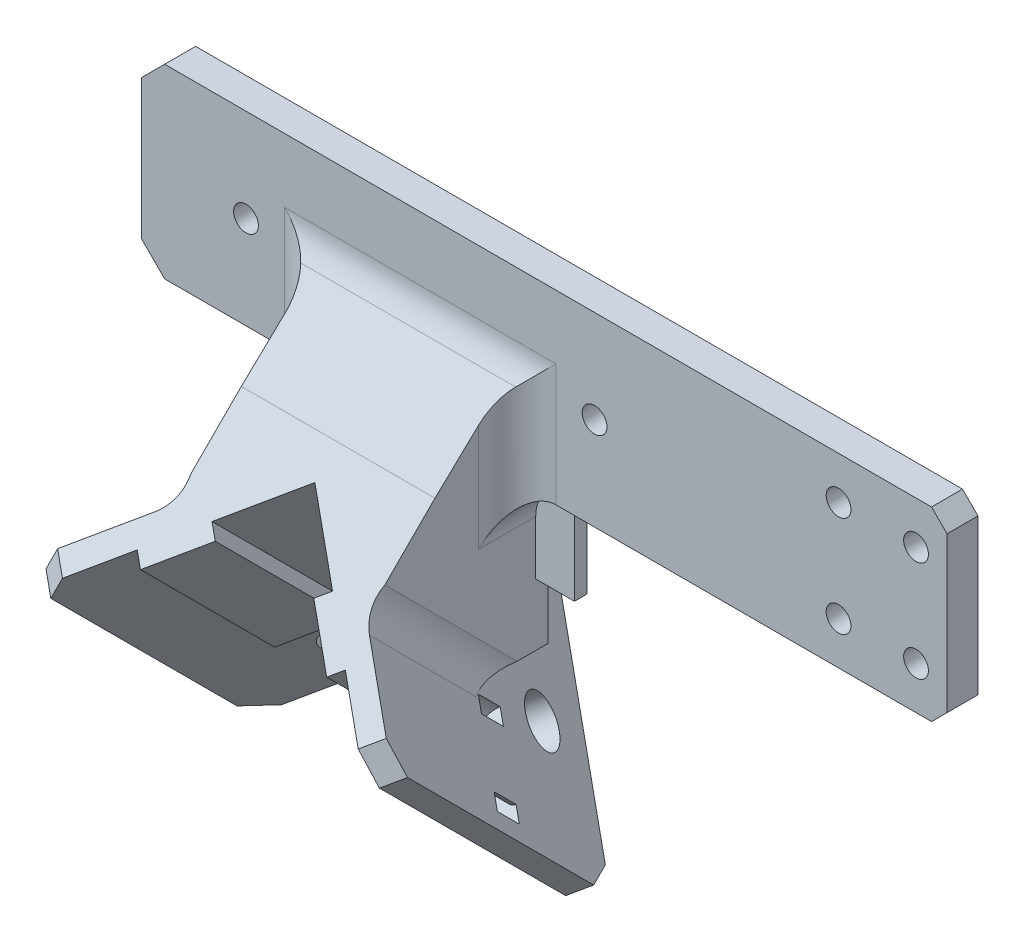
SolidWorks part; units mm, degrees
ref_plane "Alzado" through (0, 0, 0) normal (0, 0, 1) x (1, 0, 0)
ref_plane "Planta" through (0, 0, 0) normal (0, 1, 0) x (1, 0, 0)
ref_plane "Vista lateral" through (0, 0, 0) normal (1, 0, 0) x (0, 0, -1)
sketch "Croquis1" plane through (0, 0, 0) normal (0, 0, 1) x (1, 0, 0)
  line L0 (0, 0) -> (0, 18835.1574) construction
  line L1 (0, 0) -> (-18835.1574, 0) construction
  line L2 (12.5, -12) -> (36, -12)
  line L3 (-36, -12) -> (36, -12) construction
  line L4 (-36, -12) -> (-36, 12)
  line L5 (-36, 12) -> (36, 12)
  line L6 (36, -12) -> (36, 12)
  line L7 (-36, -12) -> (36, 12) construction
  line L8 (-36, 12) -> (36, -12) construction
  line L9 (-17.5, 6) -> (17.5, 6) construction
  line L10 (-17.5, 6) -> (-17.5, -6) construction
  line L11 (-17.5, -6) -> (17.5, -6) construction
  line L12 (17.5, 6) -> (17.5, -6) construction
  line L13 (-17.5, 6) -> (17.5, -6) construction
  line L14 (-17.5, -6) -> (17.5, 6) construction
  line L15 (-12.5, -32) -> (12.5, -32)
  line L16 (-12.5, -32) -> (-12.5, -12)
  line L17 (-12.5, -12) -> (12.5, -12) construction
  line L18 (12.5, -32) -> (12.5, -12)
  line L19 (-12.5, -32) -> (12.5, -12) construction
  line L20 (-12.5, -12) -> (12.5, -32) construction
  line L21 (-36, -12) -> (-12.5, -12)
  circle A0 centre (-22.5, 0) radius 1.6
  circle A1 centre (22.5, 0) radius 1.6
  point P7 (0, 0)
  point P12 (0, -22)
  point P16 (0, 0)
  dimension "D1" = 3.2
  dimension "D2" = 45
  dimension "D3" = 24
  dimension "D4" = 13.5
  dimension "D5" = 35
  dimension "D6" = 12
  dimension "D7" = 20
  dimension "D8" = 25
extrude "Saliente-Extruir1" add sketch "Croquis1" along normal blind 4
sketch "Croquis3" plane through (0, 0, 0) normal (0, 0, -1) x (-1, 0, 0)
  line L0 (0, 0) -> (-50000, 0) construction
  line L1 (-66, 12) -> (-36, 12)
  line L2 (-66, -12) -> (-36, -12)
  line L3 (-36, -12) -> (-36, 12)
  line L4 (-36, -12) -> (-36, 12) construction
  line L5 (-66, 12) -> (-68, 10)
  line L6 (-68, 10) -> (-68, -10)
  line L7 (-66, -12) -> (-68, -10)
  arc A0 (-66, 12) -> (-66, -12) centre (-66, 0) ccw construction
  circle A1 centre (-54, 6.5) radius 1.6
  circle A2 centre (-64, 6.5) radius 1.6
  circle A3 centre (-54, -6.5) radius 1.6
  circle A4 centre (-64, -6.5) radius 1.6
  point P22 (-68, 0)
  dimension "D1" = 30
  dimension "D2" = 3.2
  dimension "D5" = 28
  dimension "D3" = 13
  dimension "D4" = 18
  dimension "D6" = 32
  dimension "D7" = 2
extrude "Saliente-Extruir3" add sketch "Croquis3" against normal blind 4
ref_plane "Plano1" through (0, -4, -4) normal (0, -0.7071, -0.7071) x (1, 0, 0)
sketch "Croquis5" plane through (0, -4.201, -3.799) normal (0, 0.7071, 0.7071) x (1, 0, 0)
  line L0 (0, 0) -> (0, 50000) construction
  line L2 (-21.2132, -41.4853) -> (0, -20.2721) construction
  line L5 (-13.435, -33.7071) -> (-21.2132, -41.4853)
  line L11 (-10, -11.0294) -> (49990, -11.0294) construction
  line L12 (0, -16.0294) -> (23.3345, -39.364)
  line L13 (23.3345, -39.364) -> (21.2132, -41.4853)
  line L14 (21.2132, -41.4853) -> (0, -20.2721) construction
  line L38 (12.8592, -28.6261) -> (35368.1982, 35326.713) construction
  line L39 (0, -20.2721) -> (-7.7782, -28.0503)
  line L40 (7.7782, -28.0503) -> (6.364, -29.4645)
  line L41 (6.364, -29.4645) -> (12.0208, -35.1213)
  line L42 (12.0208, -35.1213) -> (13.435, -33.7071)
  line L43 (0, -20.2721) -> (7.7782, -28.0503)
  line L44 (13.435, -33.7071) -> (21.2132, -41.4853)
  line L45 (-12.0208, -35.1213) -> (-13.435, -33.7071)
  line L46 (-6.364, -29.4645) -> (-12.0208, -35.1213)
  line L47 (-7.7782, -28.0503) -> (-6.364, -29.4645)
  line L48 (-23.3345, -39.364) -> (-21.2132, -41.4853)
  line L49 (0, -16.0294) -> (-23.3345, -39.364)
  point P10 (0, 0)
  point P11 (0, -15.5346)
  point P13 (10.6066, -30.8787)
  point P19 (9.1924, -32.2929)
  dimension "D1" = 45
  dimension "D2" = 30
  dimension "D3" = 3
  dimension "D4" = 2
  dimension "D5" = 8
  dimension "D6" = 5
extrude "Saliente-Extruir4" add sketch "Croquis5" against normal blind 30 and the other way blind 10
sketch "Croquis13" plane through (-11.6924, -8.2678, 8.2678) normal (-0.7071, -0.5, 0.5) x (0.4082, 0.2887, 0.866)
  line L0 (-7.9932, -41.8255) -> (27113.0473, 19135.6461) construction
  line L1 (-14.3708, -41.4362) -> (-9.752, -47.9681) construction
  line L3 (18.2891, -18.3422) -> (22.9079, -24.8741) construction
  circle A0 centre (-5.5294, -40.0834) radius 3.1
  point P4 (-12.0614, -44.7022)
  point P9 (20.5985, -21.6081)
  dimension "D1" = 6.2
  dimension "D2" = 8
extrude "Cortar-Extruir8" cut sketch "Croquis13" against normal up to next
sketch "Croquis14" plane through (-11.6924, -8.2678, 8.2678) normal (-0.7071, -0.5, 0.5) x (0.4082, 0.2887, 0.866)
  line L0 (-11.513, -39.4154) -> (-6.8942, -45.9474)
  line L1 (18.2891, -18.3422) -> (-14.3708, -41.4362) construction
  line L2 (22.9079, -24.8741) -> (-9.752, -47.9681) construction
  line L3 (-6.8942, -45.9474) -> (0.4543, -40.7513)
  line L4 (22.9079, -24.8741) -> (-9.752, -47.9681) construction
  line L5 (0.4543, -40.7513) -> (-4.1645, -34.2193)
  line L6 (18.2891, -18.3422) -> (-14.3708, -41.4362) construction
  line L7 (-4.1645, -34.2193) -> (-11.513, -39.4154)
  line L8 (-7.8388, -36.8174) -> (-3.22, -43.3493) construction
  point P16 (-5.5294, -40.0834)
  dimension "D1" = 9
extrude "Cortar-Extruir9" cut sketch "Croquis14" against normal up to surface (2 mm away) up to face at (17.3241, -37.8566, 15.7145)
sketch "Croquis15" plane through (8.6283, -6.1011, 14.7678) normal (0.7071, -0.5, 0.5) x (0.6667, 0.2357, -0.7071)
  line L0 (-8.4296, -38.5546) -> (45020.4123, 18760.8677) construction
  line L2 (-23.1658, -10.0838) -> (16643.5008, -47150.5358) construction
  line L3 (-26.9371, -11.4171) -> (-19.3946, -8.7504) construction
  line L4 (-13.6037, -49.1294) -> (-6.0613, -46.4628) construction
  circle A0 centre (-12.4992, -40.2536) radius 3.1
  point P8 (-23.1658, -10.0838)
  point P11 (-9.8325, -47.7961)
  dimension "D1" = 6.2
  dimension "D2" = 8
extrude "Cortar-Extruir10" cut sketch "Croquis15" against normal up to next
sketch "Croquis17" plane through (8.6283, -6.1011, 14.7678) normal (0.7071, -0.5, 0.5) x (0.6667, 0.2357, -0.7071)
  line L0 (-14.7704, -45.8296) -> (-7.2279, -43.163)
  line L3 (-7.2279, -43.163) -> (-10.2279, -34.6777)
  line L5 (-10.2279, -34.6777) -> (-17.7704, -37.3443)
  line L7 (-17.7704, -37.3443) -> (-14.7704, -45.8296)
  line L8 (-16.2704, -41.587) -> (-8.7279, -38.9203) construction
  line L10 (-19.3946, -8.7504) -> (-6.0613, -46.4628) construction
  line L11 (-26.9371, -11.4171) -> (-13.6037, -49.1294) construction
  line L12 (-26.9371, -11.4171) -> (-13.6037, -49.1294) construction
  point P2 (-13.1428, -24.272)
  point P3 (-12.4992, -40.2536)
  point P11 (-12.4992, -40.2536)
  point P16 (-11.9894, -40.0734)
  dimension "D1" = 9
extrude "Cortar-Extruir11" cut sketch "Croquis17" against normal up to surface (2 mm away) up to face at (-17.3241, -37.8566, 15.7145)
sketch "Croquis19" plane through (0, 0, 0) normal (1, 0, 0) x (0, 0, -1)
  line L0 (-14.6066, -8.4645) -> (-21.0711, -14.9289)
  line L2 (-21.0711, -14.9289) -> (-4, -32)
  line L3 (-4, -32) -> (-4, -12) construction
  line L4 (-4, -32) -> (-4, 1.6)
  line L6 (-4, 1.6) -> (-14.6066, -8.4645)
  line L8 (-4, -19.0711) -> (-4, -32) construction
  line L9 (-14.6066, -8.4645) -> (-31.1066, -24.9645) construction
  point P3 (-19.3211, -13.1789)
  point P4 (-18.4033, -12.2612)
  point P5 (-19.3211, -13.1789)
  point P10 (-4, 1.6)
  point P11 (0, 0)
  point P14 (-4, -26.1421)
  point P17 (-19.3211, -13.1789)
  point P18 (0, 0)
  point P19 (-4, -26.1421)
  point P21 (0, 0)
  point P22 (0, 0)
  point P24 (0, 0)
  point P25 (0, 0)
  point P26 (0, 0)
  point P27 (-4, -32)
  point P29 (0, 0)
extrude "Saliente-Extruir5" add sketch "Croquis19" along normal mid plane 25
sketch "Croquis18" plane through (0, 3.0711, 3.0711) normal (0, 0.7071, 0.7071) x (1, 0, 0)
  line L7 (0, -20.5563) -> (4.8995, -25.4558)
  line L10 (4.8995, -25.4558) -> (-4.8995, -25.4558)
  line L11 (0, -20.5563) -> (-4.8995, -25.4558)
  point P1 (0, 0)
  point P2 (0, 0)
  point P3 (-4.8995, -25.4558)
  point P4 (0, 0)
  point P5 (-1.1786, -21.0468)
  point P7 (4.8995, -25.4558)
  point P8 (0, -20.5563)
extrude "Cortar-Extruir12" cut sketch "Croquis18" against normal through all
fillet "Redondeo1" radius 5 7 edges at (12.5, -5.2, 4) (-12.5, -5.2, 4) (9.1421, -23.4645, 12.5355) (-9.1421, -23.4645, 12.5355) (-12.5, -12, 2) (12.5, -12, 2) (0, 1.6, 4)
chamfer "Chaflán1" distance 3 angle 45 10 edges at (22.2739, -25.7145, 31.8566) (22.2739, -53.9987, 3.5723) (-22.2739, -25.7145, 31.8566) (-22.2739, -53.9987, 3.5723) (-36, -12, 2) (-36, 12, 2) (9.1924, -39.4099, 6.6612) (-9.1924, -39.4099, 6.6612) (-9.1924, -45.7739, 0.2972) (9.1924, -45.7739, 0.2972)
fillet "Redondeo2" [suppressed] radius 5
sketch "Croquis20" plane through (0, 0, 0) normal (0, 0, -1) x (-1, 0, 0)
  line L0 (0, 0) -> (0, 50000) construction
  line L1 (-17.5, -12) -> (49982.5, -12) construction
  line L2 (-42.5097, -24) -> (49957.4903, -24) construction
  line L4 (-17.5, -24) -> (17.5, -24)
  line L5 (-17.5, -24) -> (-17.5, -12)
  line L6 (-17.5, -12) -> (17.5, -12)
  line L7 (17.5, -24) -> (17.5, -12)
  line L8 (-17.5, -24) -> (17.5, -12) construction
  line L9 (-17.5, -12) -> (17.5, -24) construction
  point P8 (0, -18)
  point P13 (33, -24)
  point P14 (0, 0)
  point P16 (17.5, -12)
  dimension "D1" = 12
extrude "Saliente-Extruir6" add sketch "Croquis20" against normal blind 1.6
sketch "Croquis23" plane through (0, -25.2132, -25.2132) normal (0, -0.7071, -0.7071) x (1, 0, 0)
  line L0 (21.2132, 37.5269) -> (0, 16.3137) construction
  line L1 (14.92, 32.6479) -> (19.0919, 36.8198)
  line L2 (23.3345, 39.6482) -> (21.2132, 37.5269) construction
  line L3 (17.6777, 38.234) -> (13.5057, 34.0621)
  line L4 (13.5057, 29.8194) -> (14.92, 31.2337)
  line L5 (20.5061, 36.8198) -> (21.9203, 38.234)
  line L6 (13.435, 33.9914) -> (19.0919, 39.6482) construction
  line L7 (21.2132, 41.7696) -> (23.3345, 39.6482) construction
  arc A0 (14.92, 31.2337) -> (14.92, 32.6479) centre (15.6271, 31.9408) cw
  arc A1 (19.0919, 36.8198) -> (20.5061, 36.8198) centre (19.799, 36.1127) cw
  arc A2 (21.9203, 38.234) -> (17.6777, 38.234) centre (19.799, 36.1127) ccw
  arc A3 (13.5057, 34.0621) -> (13.5057, 29.8194) centre (15.6271, 31.9408) ccw
  point P15 (19.4534, 35.7671)
  point P16 (15.6424, 31.9561)
  point P17 (0, 0)
  point P18 (16.2749, 32.5886)
  point P19 (17.6464, 38.2028)
  dimension "D1" = 2
  dimension "D3" = 2
  dimension "D2" = 2
extrude "Cortar-Extruir13" cut sketch "Croquis23" against normal blind 4 from offset 16 offset against normal yes
